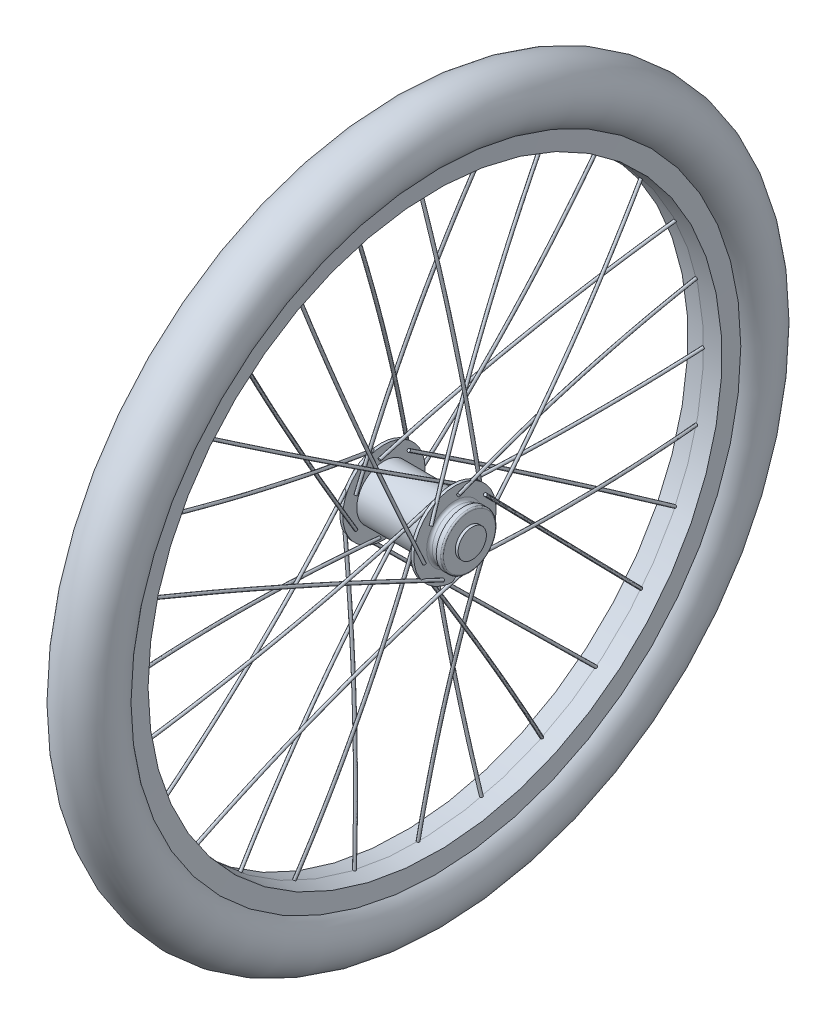
SolidWorks part; units mm, degrees
ref_plane "Front" through (0, 0, 0) normal (0, 0, 1) x (1, 0, 0)
ref_plane "Top" through (0, 0, 0) normal (0, 1, 0) x (1, 0, 0)
ref_plane "Right" through (0, 0, 0) normal (1, 0, 0) x (0, 0, -1)
ref_axis "Axis1" through (-80.9, 0, 0) along (1, 0, 0)
sketch "Sketch1" plane through (0, 0, 0) normal (0, 0, 1) x (1, 0, 0)
  line L1 (0, 253.3345) -> (0, 0) construction
  line L3 (12, 202.6) -> (12.5, 215.46)
  line L4 (-12, 202.6) -> (-12.5, 215.46)
  line L5 (0, 0) -> (109.3753, 0) construction
  line L6 (12, 202.6) -> (0, 201.6)
  line L7 (0, 201.6) -> (-12, 202.6)
  arc A0 (-12.5, 215.46) -> (12.5, 215.46) centre (0, 232.3345) cw
  circle A1 centre (0, 232.3345) radius 21 construction
  point P2 (0, 253.3345)
  point P8 (-21, 232.3345)
  dimension "D3" = 42
  dimension "D1" = 24
  dimension "D2" = 25
  dimension "D4" = 1
  dimension "D5" = 12.86
  dimension "D6" = 202.6
revolve "Revolve1" add sketch "Sketch1" angle 360 about L5
sketch "Sketch4" plane through (0, 0, 0) normal (0, 0, 1) x (1, 0, 0)
  line L1 (26.125, 0) -> (26.125, 29.075)
  line L2 (26.125, 29.075) -> (24.075, 29.075)
  line L3 (24.075, 29.075) -> (24.075, 19.14)
  line L4 (24.075, 19.14) -> (0, 19.14)
  line L5 (0, 19.14) -> (0, 0)
  line L6 (0, 253.3345) -> (0, 0) construction
  line L7 (0, 0) -> (60.5569, 0) construction
  line L8 (26.125, 0) -> (0, 0)
  line L9 (0, 0) -> (0, -24.7201) construction
  line L10 (0, 0) -> (109.3753, 0) construction
  dimension "D1" = 52.25
  dimension "D2" = 2.05
  dimension "D3" = 38.28
  dimension "D4" = 58.15
revolve "Revolve2" add sketch "Sketch4" angle 360 about L5
mirror "Mirror2" about plane through (0, 0, 0) normal (1, 0, 0) of bodies 109
sketch "Sketch5" plane through (0, 0, 0) normal (1, 0, 0) x (0, 0, -1)
  circle A0 centre (0, 0) radius 201.6 construction
  circle A1 centre (0, 0) radius 24.5 construction
  point P4 (0, 201.6)
  point P6 (0, 0)
  point P7 (0, 24.5)
  point P8 (87.471, 181.6353)
  point P11 (10.6302, 22.0737)
  point P12 (157.6172, 125.6955)
  point P13 (19.1549, 15.2755)
  point P14 (196.5455, 44.8602)
  point P15 (23.8857, 5.4518)
  point P16 (196.5455, -44.8602)
  point P17 (23.8857, -5.4518)
  point P18 (157.6172, -125.6955)
  point P19 (19.1549, -15.2755)
  point P20 (87.471, -181.6353)
  point P21 (10.6302, -22.0737)
  point P22 (0, -201.6)
  point P23 (0, -24.5)
  point P24 (-87.471, -181.6353)
  point P25 (-10.6302, -22.0737)
  point P26 (-157.6172, -125.6955)
  point P27 (-19.1549, -15.2755)
  point P28 (-196.5455, -44.8602)
  point P29 (-23.8857, -5.4518)
  point P30 (-196.5455, 44.8602)
  point P31 (-23.8857, 5.4518)
  point P32 (-157.6172, 125.6955)
  point P33 (-19.1549, 15.2755)
  point P34 (-87.471, 181.6353)
  point P35 (-10.6302, 22.0737)
  point P36 (0, 0)
  dimension "D1" = 49
  dimension "D2" = 14
ref_plane "Plane1" through (28.425, 0, 0) normal (1, 0, 0) x (0, 0, -1)
ref_plane "Plane2" through (21.775, 0, 0) normal (-1, 0, 0) x (0, 0, 1)
sketch "Sketch6" plane through (28.425, 0, 0) normal (1, 0, 0) x (0, 0, -1)
  point P0 (-19.1549, 15.2755)
  point P2 (-23.8857, -5.4518)
  point P4 (-10.6302, -22.0737)
  point P6 (10.6302, -22.0737)
  point P8 (23.8857, -5.4518)
  point P10 (19.1549, 15.2755)
  point P12 (0, 24.5)
sketch "Sketch7" plane through (21.775, 0, 0) normal (-1, 0, 0) x (0, 0, 1)
  point P0 (10.6302, 22.0737)
  point P2 (23.8857, 5.4518)
  point P4 (19.1549, -15.2755)
  point P6 (0, -24.5)
  point P8 (-19.1549, -15.2755)
  point P10 (-23.8857, 5.4518)
  point P12 (-10.6302, 22.0737)
sketch3d "3DSketch2"
  line L0 (0, 181.6353, -87.471) -> (28.425, 15.2755, 19.1549)
  line L1 (0, 201.6, 0) -> (21.775, 5.4518, -23.8857)
  line L2 (19.0509, 70.1383, -16.0086) -> (14.594, 70.1383, -16.0086)
  point P12 (16.8224, 70.1383, -16.0086)
sketch3d "3DSketch3"
  line L0 (17.8224, 70.1383, -16.0086) -> (15.8224, 70.1383, -16.0086)
  spline S0 degree 2 poles (28.425, 15.2755, 19.1549) (7.0968, 97.5195, -33.5582) (0, 181.6353, -87.471) knots 0 0 0 1 1 1
  spline S1 degree 2 poles (21.775, 5.4518, -23.8857) (18.1309, 104.2268, -11.8575) (0, 201.6, 0) knots 0 0 0 1 1 1
  point P4 (16.8224, 70.1383, -16.0086)
  dimension "D1" = 2
sketch3d "3DSketch4"
  spline S0 degree 2 poles (-259.7548, -947.0634, -139.8772) (398.9265, 137.4195, -7.8155) (-478.4746, 1073.2565, 106.145) knots -4.667069 -4.667069 -4.667069 5.630181 5.630181 5.630181 only from (21.775, 5.4518, -23.8857) to (0, 201.6, 0) construction
  spline S1 degree 2 poles (21.775, 5.4518, -23.8857) (18.1309, 104.2268, -11.8575) (0, 201.6, 0) knots 0 0 0 1 1 1
sweep "Sweep1" add path "3DSketch4" circular profile diameter 2 parameters "D3"=2
sketch3d "3DSketch5"
  spline S0 degree 2 poles (535.8044, -710.22, 484.1503) (-364.8154, 45.6136, -0.2899) (238.4601, 999.2548, -611.5119) knots -4.657483 -4.657483 -4.657483 5.622348 5.622348 5.622348 only from (28.425, 15.2755, 19.1549) to (0, 181.6353, -87.471) construction
  spline S1 degree 2 poles (28.425, 15.2755, 19.1549) (7.0968, 97.5195, -33.5582) (0, 181.6353, -87.471) knots 0 0 0 1 1 1
sweep "Sweep2" add path "3DSketch5" circular profile diameter 2 parameters "D3"=2
mirror "Mirror3" about plane through (0, 0, 0) normal (1, 0, 0) of bodies 111 112
move or copy body "Body-Move/Copy1" bodies to move or copy 125 126 copy no rotation origin (0, 0, 0) rotation axis (1, 0, 0) rotation angle 12.857
mirror "Mirror4" about plane through (0, 0, 0) normal (0, 0, 1) of bodies 128 127
delete or keep bodies "Body-Delete/Keep 1" type delete bodies bodies 128 127
pattern_circular "CirPattern2" count 7 over 360 about axis through (-80.9, 0, 0) along (1, 0, 0) of bodies 153 154 111 112 128 127
sketch "Sketch38" plane through (26.125, 0, 0) normal (1, 0, 0) x (0, 0, -1)
  circle A0 centre (0, 0) radius 18
  dimension "D1" = 36
extrude "Boss-Extrude1" add sketch "Sketch38" along normal blind 6.1
fillet "Fillet1" radius 2 1 edges at (26.125, 0, -18)
sketch "Sketch39" plane through (32.225, 0, 0) normal (1, 0, 0) x (0, 0, -1)
  circle A0 centre (0, 0) radius 19.35
  dimension "D1" = 38.7
extrude "Boss-Extrude2" add sketch "Sketch39" along normal blind 4.1
fillet "Fillet2" radius 1 1 edges at (36.325, 0, -19.35)
sketch "Sketch40" plane through (36.325, 0, 0) normal (1, 0, 0) x (0, 0, -1)
  circle A0 centre (0, 0) radius 10
  dimension "D1" = 20
extrude "Boss-Extrude3" add sketch "Sketch40" along normal blind 2
